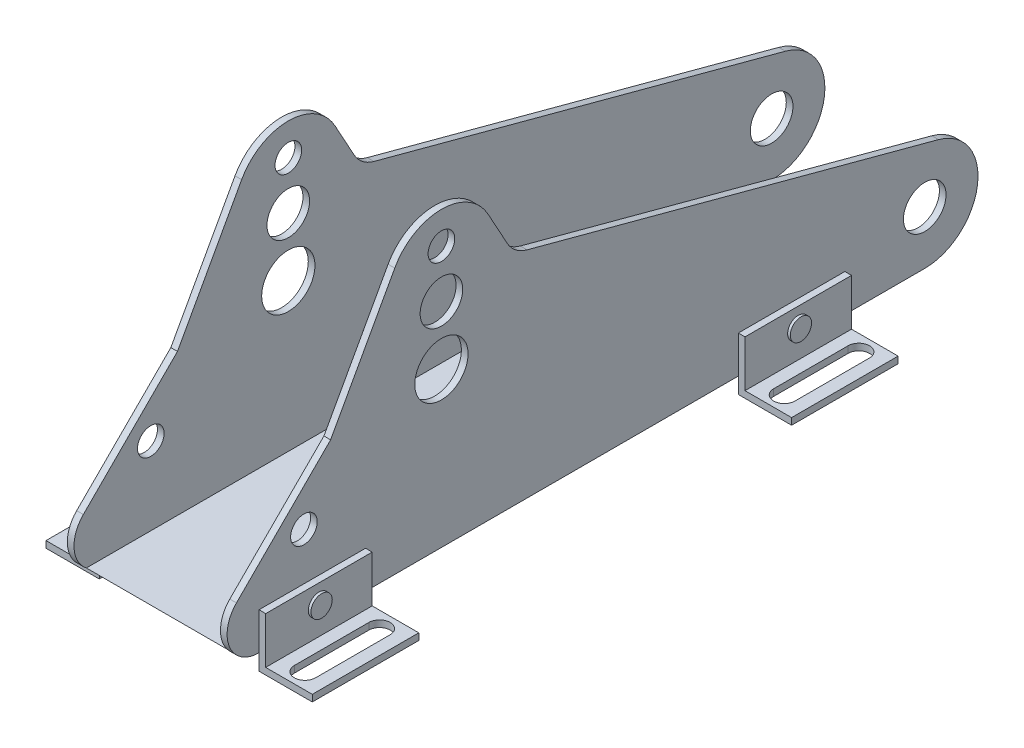
SolidWorks part; units mm, degrees
material "3.0205 (EN-AW 1200)"
ref_plane "Płaszczyzna przednia" through (0, 0, 0) normal (0, 0, 1) x (1, 0, 0)
ref_plane "Płaszczyzna górna" through (0, 0, 0) normal (0, 1, 0) x (1, 0, 0)
ref_plane "Płaszczyzna prawa" through (0, 0, 0) normal (1, 0, 0) x (0, 0, -1)
sketch "Szkic1" plane through (0, 0, 0) normal (1, 0, 0) x (0, 0, -1)
  line L0 (0, 0) -> (181.5056, 0)
  line L5 (186.682, 39.3185) -> (32.1338, 80.7296)
  line L6 (24.7305, 86.5339) -> (17.5251, 99.637)
  line L7 (-17.5251, 99.637) -> (-41.6176, 55.8244)
  line L8 (-41.6176, 55.8244) -> (-76.973, 20.469)
  line L9 (-68.4944, 0) -> (0, 0)
  arc A0 (181.5056, 0) -> (186.682, 39.3185) centre (181.5056, 20) ccw
  arc A1 (17.5251, 99.637) -> (-17.5251, 99.637) centre (0, 90) ccw
  arc A3 (-76.973, 20.469) -> (-68.4944, 0) centre (-68.4944, 11.9905) ccw
  arc A4 (32.1338, 80.7296) -> (24.7305, 86.5339) centre (35.2372, 92.3115) cw
  dimension "D1" = 90
  dimension "D4" = 160
  dimension "D8" = 20
  dimension "D9" = 45
  dimension "D7" = 20
  dimension "D2" = 15
  dimension "D3" = 250
  dimension "D5" = 50
  dimension "D6" = 50
extrude "Dodanie-wyciągnięcie1" add sketch "Szkic1" along normal blind 30 and the other way blind 30
sketch "Szkic2" plane through (0, 0, 0) normal (0, 0, 1) x (1, 0, 0)
  line L0 (30, 110) -> (-30, 110) construction
  line L1 (-27.5, 2.5035) -> (27.5, 2.5035)
  line L2 (-27.5, 2.5035) -> (-27.5, 110)
  line L3 (-27.5, 110) -> (27.5, 110)
  line L4 (27.5, 2.5035) -> (27.5, 110)
  line L5 (-30, 99.637) -> (-30, 55.8244) construction
  line L6 (30, 99.637) -> (30, 55.8244) construction
  line L7 (-30, 0) -> (30, 0) construction
  dimension "D1" = 2.5
  dimension "D2" = 2.5
  dimension "D3" = 2.5035
extrude "Wytnij-wyciągnięcie1" cut sketch "Szkic2" against normal through all and the other way through all
sketch "Szkic3" plane through (0, 0, 0) normal (0, 1, 0) x (1, 0, 0)
  line L5 (27.5, 32.1338) -> (27.5, 186.682) construction
  line L6 (-27.5, 191.1944) -> (27.5, 191.1944)
  line L7 (-27.5, 191.1944) -> (-27.5, 151.1944)
  line L8 (-27.5, 151.1944) -> (27.5, 151.1944)
  line L9 (27.5, 191.1944) -> (27.5, 151.1944)
  dimension "D1" = 40
extrude "Wytnij-wyciągnięcie3" cut sketch "Szkic3" along normal through all
sketch "Szkic4" plane through (30, 0, 0) normal (1, 0, 0) x (0, 0, -1)
  line L0 (-68.4944, 0) -> (181.5056, 0) construction
  line L1 (-68.4944, -6) -> (-28.4944, -6)
  line L2 (-68.4944, -6) -> (-68.4944, 14)
  line L3 (-68.4944, 14) -> (-28.4944, 14)
  line L4 (-28.4944, -6) -> (-28.4944, 14)
  line L5 (111.5056, -6) -> (151.5056, -6)
  line L6 (111.5056, -6) -> (111.5056, 14)
  line L7 (111.5056, 14) -> (151.5056, 14)
  line L8 (151.5056, -6) -> (151.5056, 14)
  dimension "D1" = 20
  dimension "D2" = 6
  dimension "D3" = 40
  dimension "D4" = 40
  dimension "D5" = 20
  dimension "D6" = 6
  dimension "D7" = 30
extrude "Dodanie-wyciągnięcie2" add sketch "Szkic4" along normal blind 20
sketch "Szkic5" plane through (0, 0, -151.5056) normal (0, 0, -1) x (-1, 0, 0)
  line L0 (-30, 14) -> (-30, 0) construction
  line L1 (-50, 14) -> (-32.5, 14)
  line L2 (-50, 14) -> (-50, -3.5)
  line L3 (-50, -3.5) -> (-32.5, -3.5)
  line L4 (-32.5, 14) -> (-32.5, -3.5)
  line L5 (-50, -6) -> (-30, -6) construction
  dimension "D1" = 2.5
  dimension "D2" = 2.5
extrude "Wytnij-wyciągnięcie4" cut sketch "Szkic5" against normal through all
sketch "Szkic6" plane through (32.5, 0, 0) normal (1, 0, 0) x (0, 0, -1)
  line L0 (-68.4944, 14) -> (-28.4944, 14) construction
  line L1 (111.5056, 14) -> (151.5056, 14) construction
  circle A0 centre (-48.4944, 7) radius 4
  circle A1 centre (131.5056, 7) radius 4
  point P5 (-48.4944, 14)
  point P10 (131.5056, 14)
  dimension "D1" = 8
  dimension "D3" = 8
  dimension "D2" = 7
extrude "Dodanie-wyciągnięcie3" add sketch "Szkic6" along normal blind 1
mirror "Lustro2" about plane through (0, 0, 0) normal (1, 0, 0) of "Dodanie-wyciągnięcie3", "Wytnij-wyciągnięcie4", "Dodanie-wyciągnięcie2"
sketch "Szkic7" plane through (0, -3.5, 0) normal (0, 1, 0) x (1, 0, 0)
  line L0 (-41.25, 145.5056) -> (-41.25, 117.5056) construction
  line L1 (-37.25, 145.5056) -> (-37.25, 117.5056)
  line L2 (-45.25, 145.5056) -> (-45.25, 117.5056)
  line L3 (-50, 151.5056) -> (-50, 111.5056) construction
  line L4 (-50, 151.5056) -> (-32.5, 151.5056) construction
  line L5 (-41.25, -34.4944) -> (-41.25, -62.4944) construction
  line L6 (-37.25, -34.4944) -> (-37.25, -62.4944)
  line L7 (-45.25, -34.4944) -> (-45.25, -62.4944)
  line L8 (-50, -68.4944) -> (-50, -28.4944) construction
  line L9 (-50, -28.4944) -> (-32.5, -28.4944) construction
  arc A0 (-37.25, 145.5056) -> (-45.25, 145.5056) centre (-41.25, 145.5056) ccw
  arc A1 (-45.25, 117.5056) -> (-37.25, 117.5056) centre (-41.25, 117.5056) ccw
  arc A2 (-37.25, -34.4944) -> (-45.25, -34.4944) centre (-41.25, -34.4944) ccw
  arc A3 (-45.25, -62.4944) -> (-37.25, -62.4944) centre (-41.25, -62.4944) ccw
  point P2 (-41.25, 131.5056)
  point P10 (-50, 131.5056)
  point P13 (-41.25, 151.5056)
  point P15 (-41.25, -48.4944)
  point P22 (-50, -48.4944)
  point P25 (-41.25, -28.4944)
  dimension "D1" = 8
  dimension "D2" = 28
  dimension "D3" = 28
  dimension "D4" = 8
extrude "Wytnij-wyciągnięcie5" cut sketch "Szkic7" against normal through all
mirror "Lustro3" about plane through (0, 0, 0) normal (1, 0, 0) of "Wytnij-wyciągnięcie5"
sketch "Szkic8" plane through (30, 0, 0) normal (1, 0, 0) x (0, 0, -1)
  line L0 (-59.2953, 38.1467) -> (28.8937, -35.8526) construction
  line L1 (-28.4944, 0) -> (111.5056, 0) construction
  line L2 (-41.6176, 55.8244) -> (-76.973, 20.469) construction
  circle A0 centre (0, 98) radius 5
  circle A1 centre (-51.6349, 31.7188) radius 5
  circle A2 centre (0, 80) radius 8
  arc A3 (17.5251, 99.637) -> (-17.5251, 99.637) centre (0, 90) ccw construction
  circle A4 centre (0, 58) radius 10
  circle A5 centre (181.5056, 20) radius 8
  point P11 (0, 0)
  point P21 (-59.2953, 38.1467)
  dimension "D1" = 10
  dimension "D2" = 10
  dimension "D3" = 16
  dimension "D8" = 20
  dimension "D10" = 16
  dimension "D4" = 40
  dimension "D5" = 10
  dimension "D6" = 18
  dimension "D7" = 8
  dimension "D9" = 22
extrude "Wytnij-wyciągnięcie6" cut sketch "Szkic8" against normal through all
